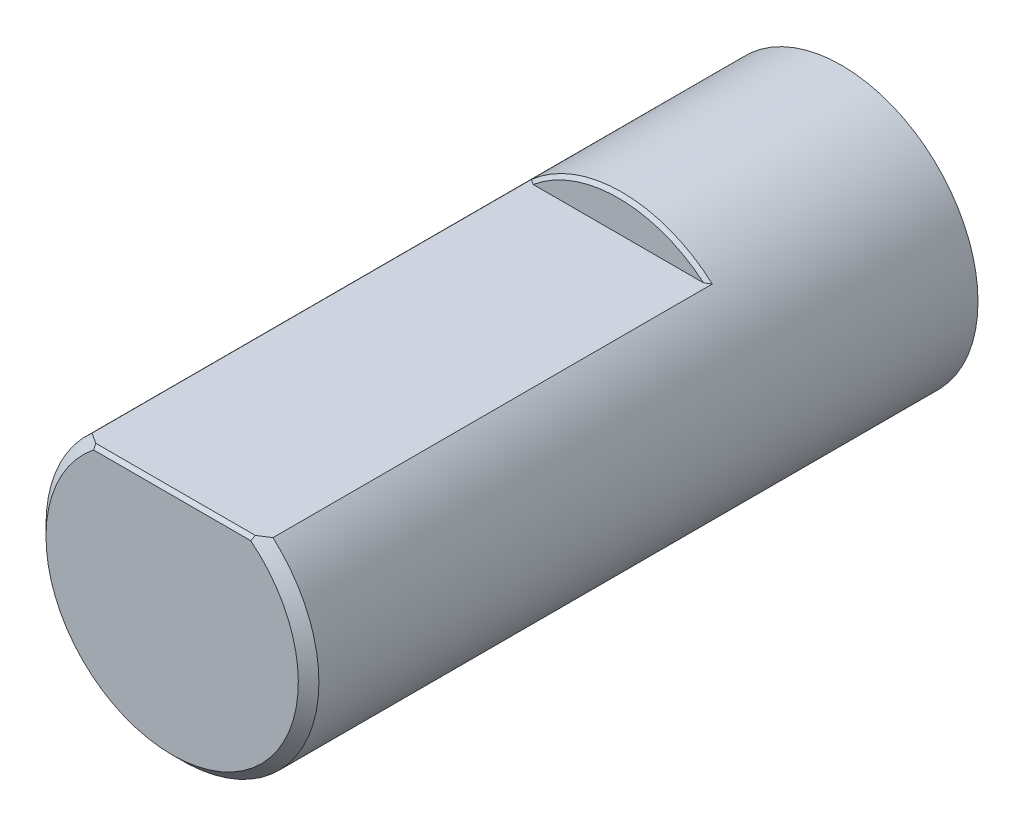
SolidWorks part; units mm, degrees
material "1023 炭素鋼板 (SS)"
ref_plane "正面" through (0, 0, 0) normal (0, 0, 1) x (1, 0, 0)
ref_plane "平面" through (0, 0, 0) normal (0, 1, 0) x (1, 0, 0)
ref_plane "右側面" through (0, 0, 0) normal (1, 0, 0) x (0, 0, -1)
sketch "ｽｹｯﾁ1" plane through (0, 0, 0) normal (0, 0, 1) x (1, 0, 0)
  line L0 (-2.6363, 2.975) -> (2.6363, 2.975)
  line L1 (0, 3.975) -> (0, -3.975) construction
  circle A0 centre (0, 0) radius 3.975
  dimension "D1" = 7.95
  dimension "D2" = 6.95
extrude "ﾎﾞｽ - 押し出し1" add sketch "ｽｹｯﾁ1" along normal blind 6.5 contours L1 L0 A0 | L1 A0 L0 | L0 L1 A0 | A0 L1 L0 region at (-1.0076, 3.3797, 0) region at (-1.7404, -0.2654, 0) region at (1.0076, 3.3797, 0) region at (1.7404, -0.2654, 0)
extrude "ﾎﾞｽ - 押し出し2" add sketch "ｽｹｯﾁ1<3>" along normal blind 13 from surface contours L0 L1 A0 | L1 L0 A0 region at (-1.7404, -0.2654, 0) region at (1.7404, -0.2654, 0) starting at face at (3.975, 0, 6.5)
sketch "ｽｹｯﾁ1<3>" plane through (0, 0, 0) normal (0, 0, 1) x (1, 0, 0) same geometry as "ｽｹｯﾁ1"
chamfer "面取り9" distance 0.1 angle 45 2 edges at (0, 2.975, 19.5) (0, 3.975, 6.5)
chamfer "面取り1" distance 0.3 angle 45 1 edges at (0, -3.975, 19.5)
